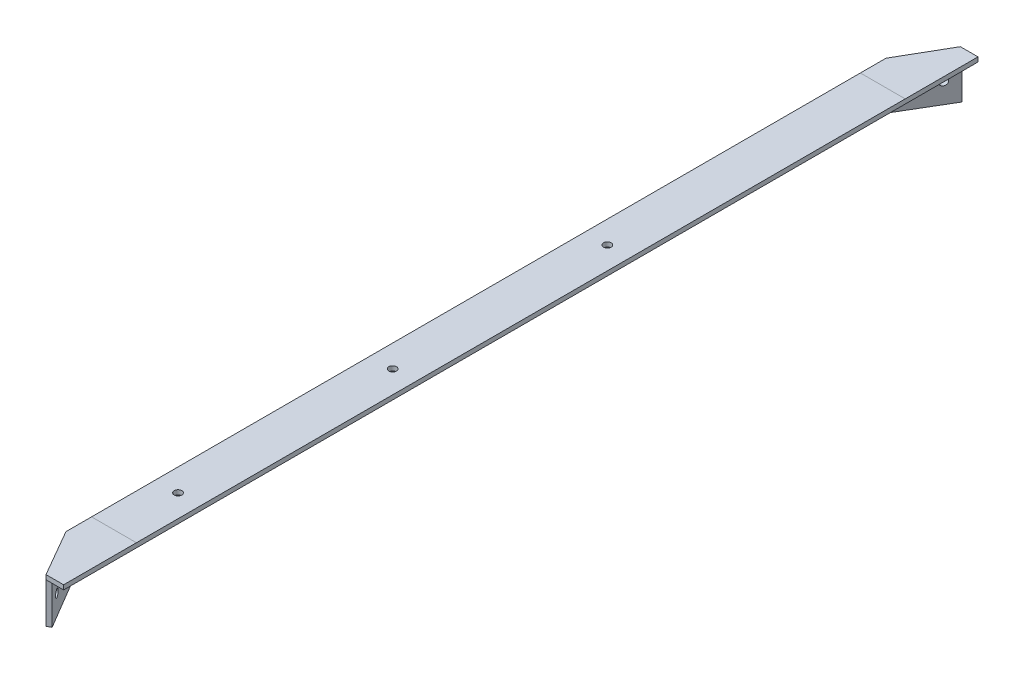
SolidWorks part; units mm, degrees
material "1.0116 (S235J2G3)"
ref_plane "Front Plane" through (0, 0, 0) normal (0, 0, 1) x (1, 0, 0)
ref_plane "Top Plane" through (0, 0, 0) normal (0, 1, 0) x (1, 0, 0)
ref_plane "Right Plane" through (0, 0, 0) normal (1, 0, 0) x (0, 0, -1)
sketch "Sketch1" plane through (0, 0, 0) normal (0, 0, 1) x (1, 0, 0)
  line L6 (0, 0) -> (0, 70)
  line L7 (0, 70) -> (70, 70)
  line L8 (70, 70) -> (70, 63)
  line L9 (70, 63) -> (7, 63)
  line L10 (7, 63) -> (7, 0)
  line L11 (7, 0) -> (0, 0)
  dimension "D1" = 70
  dimension "D2" = 70
  dimension "D3" = 7
  dimension "D4" = 7
extrude "Boss-Extrude1" add sketch "Sketch1" along normal blind 640
sketch "Sketch21" plane through (0, 0, 0) normal (0, 0, -1) x (-1, 0, 0)
  line L0 (0, 70) -> (-70, 70) construction
  line L1 (-70, 70) -> (-70, 0) construction
  line L2 (-70, 0) -> (0, 0) construction
  line L3 (0, 0) -> (0, 69.2595) construction
sketch "Sketch23" plane through (0, 0, 0) normal (0, 1, 0) x (1, 0, 0)
  line L0 (0, -640) -> (42.5, -713.6122)
  line L1 (42.5, -713.6122) -> (48.5622, -710.1122)
  line L2 (48.5622, -710.1122) -> (7, -640)
  line L3 (7, -640) -> (0, -640)
  line L4 (0, -38.5) -> (0, 38.5) construction
  dimension "D1" = 7
  dimension "D2" = 210
  dimension "D3" = 85
extrude "Boss-Extrude2" add sketch "Sketch23" along normal blind 63
sketch "Sketch25" plane through (0, 63, 0) normal (0, 1, 0) x (1, 0, 0)
  line L0 (70, -640) -> (0, -640)
  line L1 (70, -640) -> (70, 0) construction
  line L2 (7, -640) -> (70, -640) construction
  line L3 (0, -640) -> (42.5, -713.6122) construction
  line L4 (0, -640) -> (42.5, -713.6122)
  line L5 (42.5, -713.6122) -> (48.5622, -710.1122) construction
  line L6 (42.5, -713.6122) -> (70, -713.6122)
  line L7 (70, -713.6122) -> (70, -640)
extrude "Boss-Extrude3" add sketch "Sketch25" along normal blind 7
sketch "Sketch26" plane through (-275.5567, 0, 163.3488) normal (0.8602, 0, -0.5099) x (-0.5099, 0, -0.8602)
  line L0 (-635.6125, 0) -> (-554.1071, 0) construction
  line L1 (-635.6125, 63) -> (-635.6125, 0) construction
  line L2 (-554.1071, 0) -> (-554.1071, 63) construction
  circle A0 centre (-614.3625, 31.5) radius 6
  circle A1 centre (-575.3571, 31.5) radius 6
  dimension "D1" = 12
  dimension "D2" = 12
  dimension "D3" = 31.5
  dimension "D4" = 31.5
  dimension "D5" = 21.25
  dimension "D6" = 21.25
extrude "Cut-Extrude2" cut sketch "Sketch26" against normal blind 10
mirror "Mirror1" about plane through (0, 0, 0) normal (0, 0, 1) of bodies 119 116
sketch "Sketch28" plane through (0, 70, 0) normal (0, 1, 0) x (1, 0, 0)
  line L0 (70, -713.6122) -> (70, 713.6122) construction
  circle A0 centre (35, -500) radius 6
  circle A1 centre (35, -165) radius 6
  circle A2 centre (35, 170) radius 6
  dimension "D1" = 12
  dimension "D2" = 12
  dimension "D3" = 12
  dimension "D4" = 335
  dimension "D5" = 335
  dimension "D6" = 500
  dimension "D7" = 35
  dimension "D8" = 35
  dimension "D9" = 35
extrude "Cut-Extrude1" cut sketch "Sketch28" against normal blind 10 and the other way blind 10
sketch "Sketch29" plane through (0, 70, 0) normal (0, 1, 0) x (1, 0, 0)
  line L0 (0, 600.0022) -> (70, 600.0022)
  line L1 (0, -38.5) -> (0, 38.5) construction
  line L2 (70, -713.6122) -> (70, 713.6122) construction
  line L3 (70, 600.0022) -> (70, -600.0022)
  line L4 (70, -600.0022) -> (0, -600.0022)
  line L5 (0, -600.0022) -> (0, 600.0022)
  line L6 (42.5, 713.6122) -> (70, 713.6122) construction
  line L7 (42.5, -713.6122) -> (70, -713.6122) construction
  dimension "D1" = 113.61
  dimension "D2" = 113.61
split line "Split Line1"
